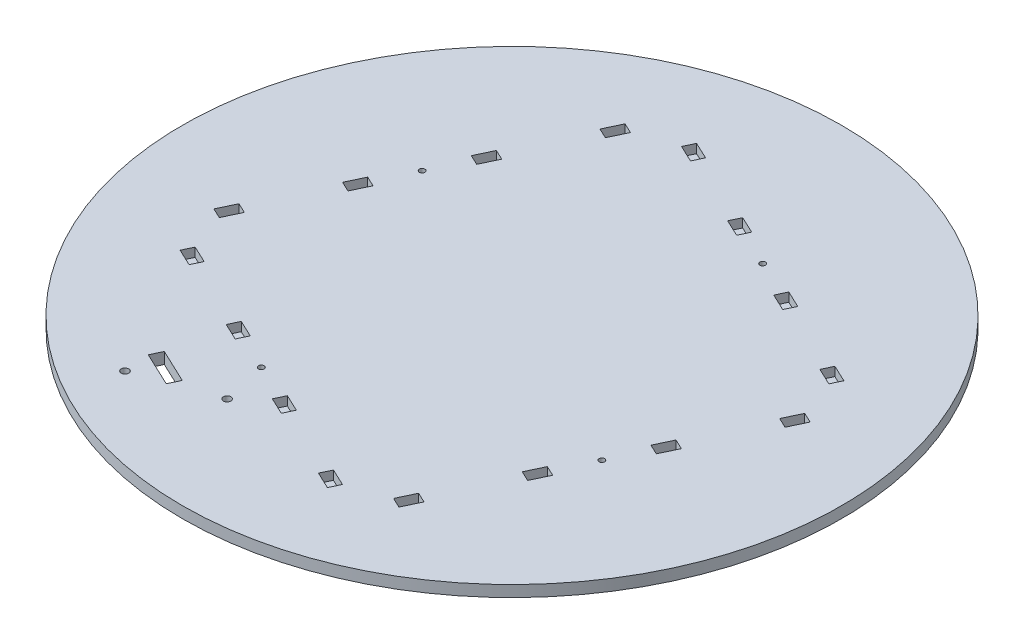
SolidWorks part; units mm, degrees
material "Oak"
ref_plane "Front Plane" through (0, 0, 0) normal (0, 0, 1) x (1, 0, 0)
ref_plane "Top Plane" through (0, 0, 0) normal (0, 1, 0) x (1, 0, 0)
ref_plane "Right Plane" through (0, 0, 0) normal (1, 0, 0) x (0, 0, -1)
sketch "Sketch1" plane through (0, 0, 0) normal (0, 1, 0) x (1, 0, 0)
  circle A0 centre (0, 0) radius 175
  dimension "D1" = 350
extrude "Boss-Extrude1" add sketch "Sketch1" along normal blind 6
sketch "Sketch2" plane through (0, 6, 0) normal (0, 1, 0) x (1, 0, 0)
  line L0 (32.7078, -122.7322) -> (23.6661, -118.4606) construction
  line L1 (23.6661, -118.4606) -> (21.1031, -123.8857) construction
  line L2 (21.1031, -123.8857) -> (30.1449, -128.1573) construction
  line L3 (30.1449, -128.1573) -> (32.7078, -122.7322) construction
  line L4 (-13.7065, -100.8046) -> (-22.7483, -96.533) construction
  line L5 (-22.7483, -96.533) -> (-25.3112, -101.9581) construction
  line L6 (-25.3112, -101.9581) -> (-16.2695, -106.2297) construction
  line L7 (-16.2695, -106.2297) -> (-13.7065, -100.8046) construction
  line L8 (-106.5352, -56.9495) -> (-115.577, -52.6779) construction
  line L9 (-115.577, -52.6779) -> (-118.14, -58.1029) construction
  line L10 (-118.14, -58.1029) -> (-109.0982, -62.3745) construction
  line L11 (-109.0982, -62.3745) -> (-106.5352, -56.9495) construction
  line L12 (-100.8046, 13.7065) -> (-96.533, 22.7483) construction
  line L13 (-96.533, 22.7483) -> (-101.9581, 25.3112) construction
  line L14 (-101.9581, 25.3112) -> (-106.2297, 16.2695) construction
  line L15 (-106.2297, 16.2695) -> (-100.8046, 13.7065) construction
  line L16 (-122.7322, -32.7078) -> (-118.4606, -23.6661) construction
  line L17 (-118.4606, -23.6661) -> (-123.8857, -21.1031) construction
  line L18 (-123.8857, -21.1031) -> (-128.1573, -30.1449) construction
  line L19 (-128.1573, -30.1449) -> (-122.7322, -32.7078) construction
  line L20 (32.7078, -122.7322) -> (23.6661, -118.4606)
  line L21 (23.6661, -118.4606) -> (21.1031, -123.8857)
  line L22 (21.1031, -123.8857) -> (30.1449, -128.1573)
  line L23 (30.1449, -128.1573) -> (32.7078, -122.7322)
  line L24 (-13.7065, -100.8046) -> (-22.7483, -96.533)
  line L25 (-22.7483, -96.533) -> (-25.3112, -101.9581)
  line L26 (-25.3112, -101.9581) -> (-16.2695, -106.2297)
  line L27 (-16.2695, -106.2297) -> (-13.7065, -100.8046)
  line L28 (-106.5352, -56.9495) -> (-115.577, -52.6779)
  line L29 (-115.577, -52.6779) -> (-118.14, -58.1029)
  line L30 (-118.14, -58.1029) -> (-109.0982, -62.3745)
  line L31 (-109.0982, -62.3745) -> (-106.5352, -56.9495)
  line L32 (-100.8046, 13.7065) -> (-96.533, 22.7483)
  line L33 (-96.533, 22.7483) -> (-101.9581, 25.3112)
  line L34 (-101.9581, 25.3112) -> (-106.2297, 16.2695)
  line L35 (-106.2297, 16.2695) -> (-100.8046, 13.7065)
  line L36 (-122.7322, -32.7078) -> (-118.4606, -23.6661)
  line L37 (-118.4606, -23.6661) -> (-123.8857, -21.1031)
  line L38 (-123.8857, -21.1031) -> (-128.1573, -30.1449)
  line L39 (-128.1573, -30.1449) -> (-122.7322, -32.7078)
  line L40 (106.5352, 56.9495) -> (115.577, 52.6779) construction
  line L41 (115.577, 52.6779) -> (118.14, 58.1029) construction
  line L42 (118.14, 58.1029) -> (109.0982, 62.3745) construction
  line L43 (109.0982, 62.3745) -> (106.5352, 56.9495) construction
  line L44 (-56.9495, 106.5352) -> (-52.6779, 115.577) construction
  line L45 (-52.6779, 115.577) -> (-58.1029, 118.14) construction
  line L46 (-58.1029, 118.14) -> (-62.3745, 109.0982) construction
  line L47 (-62.3745, 109.0982) -> (-56.9495, 106.5352) construction
  line L48 (60.1209, 78.8771) -> (69.1626, 74.6055) construction
  line L49 (69.1626, 74.6055) -> (71.7256, 80.0305) construction
  line L50 (71.7256, 80.0305) -> (62.6838, 84.3021) construction
  line L51 (62.6838, 84.3021) -> (60.1209, 78.8771) construction
  line L52 (13.7065, 100.8046) -> (22.7483, 96.533) construction
  line L53 (22.7483, 96.533) -> (25.3112, 101.9581) construction
  line L54 (25.3112, 101.9581) -> (16.2695, 106.2297) construction
  line L55 (16.2695, 106.2297) -> (13.7065, 100.8046) construction
  line L56 (-32.7078, 122.7322) -> (-23.6661, 118.4606) construction
  line L57 (-23.6661, 118.4606) -> (-21.1031, 123.8857) construction
  line L58 (-21.1031, 123.8857) -> (-30.1449, 128.1573) construction
  line L59 (-30.1449, 128.1573) -> (-32.7078, 122.7322) construction
  line L60 (-78.8771, 60.1209) -> (-74.6055, 69.1626) construction
  line L61 (-74.6055, 69.1626) -> (-80.0305, 71.7256) construction
  line L62 (-80.0305, 71.7256) -> (-84.3021, 62.6838) construction
  line L63 (-84.3021, 62.6838) -> (-78.8771, 60.1209) construction
  line L64 (-60.1209, -78.8771) -> (-69.1626, -74.6055) construction
  line L65 (-69.1626, -74.6055) -> (-71.7256, -80.0305) construction
  line L66 (-71.7256, -80.0305) -> (-62.6838, -84.3021) construction
  line L67 (-62.6838, -84.3021) -> (-60.1209, -78.8771) construction
  line L68 (122.7322, 32.7078) -> (118.4606, 23.6661) construction
  line L69 (118.4606, 23.6661) -> (123.8857, 21.1031) construction
  line L70 (123.8857, 21.1031) -> (128.1573, 30.1449) construction
  line L71 (128.1573, 30.1449) -> (122.7322, 32.7078) construction
  line L72 (100.8046, -13.7065) -> (96.533, -22.7483) construction
  line L73 (96.533, -22.7483) -> (101.9581, -25.3112) construction
  line L74 (101.9581, -25.3112) -> (106.2297, -16.2695) construction
  line L75 (106.2297, -16.2695) -> (100.8046, -13.7065) construction
  line L76 (78.8771, -60.1209) -> (74.6055, -69.1626) construction
  line L77 (74.6055, -69.1626) -> (80.0305, -71.7256) construction
  line L78 (80.0305, -71.7256) -> (84.3021, -62.6838) construction
  line L79 (84.3021, -62.6838) -> (78.8771, -60.1209) construction
  line L80 (56.9495, -106.5352) -> (52.6779, -115.577) construction
  line L81 (52.6779, -115.577) -> (58.1029, -118.14) construction
  line L82 (58.1029, -118.14) -> (62.3745, -109.0982) construction
  line L83 (62.3745, -109.0982) -> (56.9495, -106.5352) construction
  line L84 (106.5352, 56.9495) -> (115.577, 52.6779)
  line L85 (115.577, 52.6779) -> (118.14, 58.1029)
  line L86 (118.14, 58.1029) -> (109.0982, 62.3745)
  line L87 (109.0982, 62.3745) -> (106.5352, 56.9495)
  line L88 (-56.9495, 106.5352) -> (-52.6779, 115.577)
  line L89 (-52.6779, 115.577) -> (-58.1029, 118.14)
  line L90 (-58.1029, 118.14) -> (-62.3745, 109.0982)
  line L91 (-62.3745, 109.0982) -> (-56.9495, 106.5352)
  line L92 (60.1209, 78.8771) -> (69.1626, 74.6055)
  line L93 (69.1626, 74.6055) -> (71.7256, 80.0305)
  line L94 (71.7256, 80.0305) -> (62.6838, 84.3021)
  line L95 (62.6838, 84.3021) -> (60.1209, 78.8771)
  line L96 (13.7065, 100.8046) -> (22.7483, 96.533)
  line L97 (22.7483, 96.533) -> (25.3112, 101.9581)
  line L98 (25.3112, 101.9581) -> (16.2695, 106.2297)
  line L99 (16.2695, 106.2297) -> (13.7065, 100.8046)
  line L100 (-32.7078, 122.7322) -> (-23.6661, 118.4606)
  line L101 (-23.6661, 118.4606) -> (-21.1031, 123.8857)
  line L102 (-21.1031, 123.8857) -> (-30.1449, 128.1573)
  line L103 (-30.1449, 128.1573) -> (-32.7078, 122.7322)
  line L104 (-78.8771, 60.1209) -> (-74.6055, 69.1626)
  line L105 (-74.6055, 69.1626) -> (-80.0305, 71.7256)
  line L106 (-80.0305, 71.7256) -> (-84.3021, 62.6838)
  line L107 (-84.3021, 62.6838) -> (-78.8771, 60.1209)
  line L108 (-60.1209, -78.8771) -> (-69.1626, -74.6055)
  line L109 (-69.1626, -74.6055) -> (-71.7256, -80.0305)
  line L110 (-71.7256, -80.0305) -> (-62.6838, -84.3021)
  line L111 (-62.6838, -84.3021) -> (-60.1209, -78.8771)
  line L112 (122.7322, 32.7078) -> (118.4606, 23.6661)
  line L113 (118.4606, 23.6661) -> (123.8857, 21.1031)
  line L114 (123.8857, 21.1031) -> (128.1573, 30.1449)
  line L115 (128.1573, 30.1449) -> (122.7322, 32.7078)
  line L116 (100.8046, -13.7065) -> (96.533, -22.7483)
  line L117 (96.533, -22.7483) -> (101.9581, -25.3112)
  line L118 (101.9581, -25.3112) -> (106.2297, -16.2695)
  line L119 (106.2297, -16.2695) -> (100.8046, -13.7065)
  line L120 (78.8771, -60.1209) -> (74.6055, -69.1626)
  line L121 (74.6055, -69.1626) -> (80.0305, -71.7256)
  line L122 (80.0305, -71.7256) -> (84.3021, -62.6838)
  line L123 (84.3021, -62.6838) -> (78.8771, -60.1209)
  line L124 (56.9495, -106.5352) -> (52.6779, -115.577)
  line L125 (52.6779, -115.577) -> (58.1029, -118.14)
  line L126 (58.1029, -118.14) -> (62.3745, -109.0982)
  line L127 (62.3745, -109.0982) -> (56.9495, -106.5352)
extrude "Cut-Extrude1" cut sketch "Sketch2" against normal blind 4.75
sketch "Sketch3" plane through (0, 6, 0) normal (0, 1, 0) x (1, 0, 0)
  line L0 (12.4764, 52.4112) -> (39.3092, 38.9948)
  line L1 (12.4764, 52.4112) -> (41.5453, 110.549)
  line L2 (39.3092, 38.9948) -> (68.3781, 97.1326)
  line L3 (41.5453, 110.549) -> (68.3781, 97.1326)
  line L4 (23.6567, 97.1326) -> (68.3781, 130.6736)
  line L5 (68.3781, 130.6736) -> (68.3781, 74.7719)
  line L6 (68.3781, 74.7719) -> (23.6567, 97.1326)
  point P8 (25.8928, 45.703)
  dimension "D1" = 30
  dimension "D2" = 45
  dimension "D3" = 65
  dimension "D4" = 50
sketch "Sketch4" plane through (0, 6, 0) normal (0, 1, 0) x (1, 0, 0)
  line L0 (-57.681, -117.4119) -> (-75.7645, -108.8687) construction
  line L1 (-75.7645, -108.8687) -> (-78.4983, -114.6554) construction
  line L2 (-60.4148, -123.1986) -> (-57.681, -117.4119) construction
  line L3 (-78.4983, -114.6554) -> (-60.4148, -123.1986) construction
  line L4 (-57.681, -117.4119) -> (-75.7645, -108.8687)
  line L5 (-75.7645, -108.8687) -> (-78.4983, -114.6554)
  line L6 (-60.4148, -123.1986) -> (-57.681, -117.4119)
  line L7 (-78.4983, -114.6554) -> (-60.4148, -123.1986)
  circle A0 centre (-77.2096, -128.3148) radius 2 construction
  circle A1 centre (-37.2695, -114.0043) radius 2 construction
  circle A2 centre (-77.2096, -128.3148) radius 2
  circle A3 centre (-37.2695, -114.0043) radius 2
extrude "Cut-Extrude2" cut sketch "Sketch4" against normal through all
sketch "Sketch5" plane through (0, 6, 0) normal (0, 1, 0) x (1, 0, 0)
  line L0 (44.0723, 89.7768) -> (41.3598, 91.0583) construction
  line L1 (42.7908, 87.0643) -> (45.3538, 92.4894) construction
  line L4 (40.0783, 88.3458) -> (42.6413, 93.7708) construction
  line L5 (40.0783, 88.3458) -> (42.6413, 93.7708) construction
  line L6 (42.7908, 87.0643) -> (45.3538, 92.4894) construction
  circle A0 centre (42.7161, 90.4176) radius 1.5
  circle A1 centre (90.4176, -42.7161) radius 1.5
  circle A2 centre (-42.7161, -90.4176) radius 1.5
  circle A3 centre (-90.4176, 42.7161) radius 1.5
  point P4 (42.7161, 90.4176)
  dimension "D1" = 3
  dimension "D2" = 4
extrude "Cut-Extrude3" cut sketch "Sketch5" against normal through all
